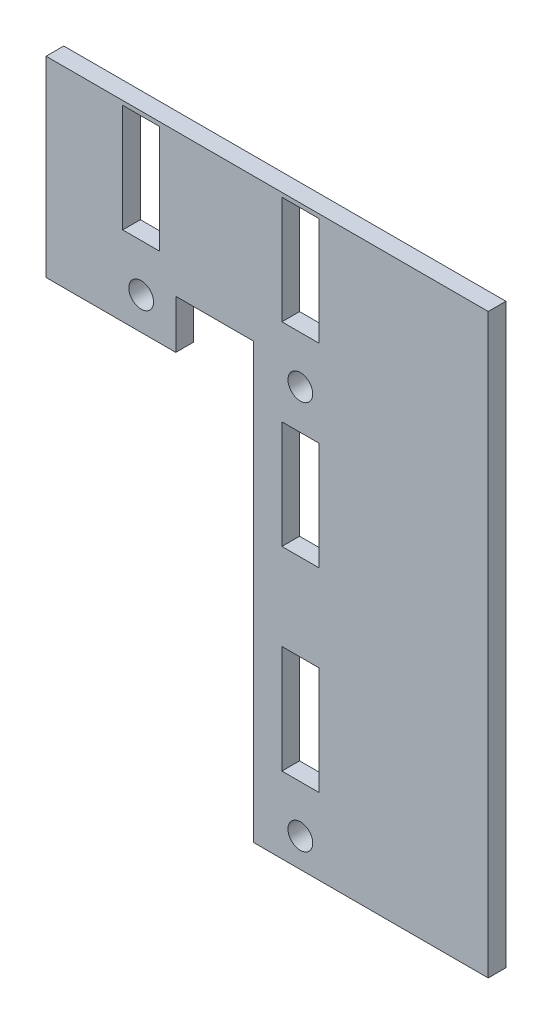
SolidWorks part; units mm, degrees
ref_plane "Front Plane" through (0, 0, 0) normal (1, 0, 0) x (0, 1, 0)
ref_plane "Top Plane" through (0, 0, 0) normal (0, 0, 1) x (0, 1, 0)
ref_plane "Right Plane" through (0, 0, 0) normal (0, 1, 0) x (-1, 0, 0)
sketch "Sketch1" plane through (0, 0, 0) normal (0, 0, 1) x (0, 1, 0)
  line L1 (-50.8, 25.4) -> (50.8, 25.4)
  line L2 (-50.8, 25.4) -> (-50.8, -25.4)
  line L3 (-50.8, -25.4) -> (50.8, -25.4)
  line L4 (50.8, 25.4) -> (50.8, -25.4)
  line L5 (-50.8, 25.4) -> (50.8, -25.4) construction
  line L6 (-50.8, -25.4) -> (50.8, 25.4) construction
  point P0 (0, 0)
  dimension "D1" = 101.6
  dimension "D2" = 50.8
extrude "Boss-Extrude1" add sketch "Sketch1" along normal blind 2.54
sketch "Sketch2" plane through (0, 0, 2.54) normal (0, 0, 1) x (1, 0, 0)
  line L0 (11.1159, -27.94) -> (11.1159, 27.94) construction
  line L1 (11.1159, 27.94) -> (-11.7441, 27.94) construction
  line L2 (-11.7441, 27.94) -> (-11.7441, -27.94) construction
  line L3 (-11.7441, -27.94) -> (11.1159, -27.94) construction
  line L4 (25.4, 50.8) -> (-25.4, 50.8) construction
  circle A0 centre (11.1159, 27.94) radius 1.778
  circle A1 centre (11.1159, -27.94) radius 1.778
  circle A2 centre (-11.7441, 27.94) radius 1.778
  dimension "D3" = 3.556
  dimension "D1" = 55.88
  dimension "D2" = 22.86
  dimension "D4" = 22.86
extrude "Cut-Extrude1" cut sketch "Sketch2" against normal through all
sketch "Sketch3" plane through (0, 0, 2.54) normal (0, 0, 1) x (1, 0, 0)
  line L0 (11.1159, -27.94) -> (11.1159, 27.94) construction
  line L1 (13.7659, -5.68) -> (8.4659, -5.68)
  line L2 (13.7659, -5.68) -> (13.7659, -21.18)
  line L3 (13.7659, -21.18) -> (8.4659, -21.18)
  line L4 (8.4659, -5.68) -> (8.4659, -21.18)
  line L5 (13.7659, -5.68) -> (8.4659, -21.18) construction
  line L6 (13.7659, -21.18) -> (8.4659, -5.68) construction
  line L7 (13.7659, 6.76) -> (8.4659, 6.76)
  line L8 (13.7659, 6.76) -> (13.7659, 22.26)
  line L9 (13.7659, 22.26) -> (8.4659, 22.26)
  line L10 (8.4659, 6.76) -> (8.4659, 22.26)
  line L11 (13.7659, 6.76) -> (8.4659, 22.26) construction
  line L12 (13.7659, 22.26) -> (8.4659, 6.76) construction
  line L13 (13.7659, 34.7) -> (8.4659, 34.7)
  line L14 (13.7659, 34.7) -> (13.7659, 50.2)
  line L15 (13.7659, 50.2) -> (8.4659, 50.2)
  line L16 (8.4659, 34.7) -> (8.4659, 50.2)
  line L17 (13.7659, 34.7) -> (8.4659, 50.2) construction
  line L18 (13.7659, 50.2) -> (8.4659, 34.7) construction
  line L19 (-9.0941, 34.7) -> (-14.3941, 34.7)
  line L20 (-9.0941, 34.7) -> (-9.0941, 50.2)
  line L21 (-9.0941, 50.2) -> (-14.3941, 50.2)
  line L22 (-14.3941, 34.7) -> (-14.3941, 50.2)
  line L23 (-9.0941, 34.7) -> (-14.3941, 50.2) construction
  line L24 (-9.0941, 50.2) -> (-14.3941, 34.7) construction
  circle A0 centre (11.1159, -27.94) radius 1.778 construction
  point P0 (11.1159, -13.43)
  point P10 (11.1159, 14.51)
  point P14 (11.1159, 42.45)
  point P19 (-11.7441, 42.45)
  dimension "D1" = 6.76
  dimension "D3" = 15.5
  dimension "D4" = 27.94
  dimension "D5" = 27.94
  dimension "D6" = 22.86
  dimension "D7" = 5.3
extrude "Cut-Extrude4" cut sketch "Sketch3" against normal through all
sketch "Sketch5" plane through (0, 0, 2.54) normal (0, 0, 1) x (1, 0, 0)
  line L0 (4.4019, -32.102) -> (4.4019, 30.255)
  line L1 (-25.4, -50.8) -> (25.4, -50.8) construction
  line L2 (4.4019, 30.255) -> (-6.7741, 30.255)
  line L3 (-6.7741, 30.255) -> (-6.7741, 23.27)
  line L4 (-6.7741, 23.27) -> (-25.4, 23.27)
  line L5 (-25.4, 50.8) -> (-25.4, -50.8) construction
  line L6 (-25.4, 23.27) -> (-25.4, -50.8)
  line L7 (-25.4, -50.8) -> (25.4, -50.8)
  line L8 (4.4019, -32.102) -> (25.4, -32.102)
  line L9 (25.4, -50.8) -> (25.4, 50.8) construction
  line L10 (25.4, -32.102) -> (25.4, -50.8)
  line L11 (8.4659, -21.18) -> (13.7659, -21.18) construction
  dimension "D1" = 4.064
  dimension "D2" = 4.445
  dimension "D3" = 11.43
  dimension "D4" = 15.24
  dimension "D5" = 10.922
extrude "Cut-Extrude5" cut sketch "Sketch5" against normal through all
sketch "Sketch6" plane through (0, 0, 2.54) normal (0, 0, 1) x (1, 0, 0)
  line L7 (25.4, 50.8) -> (38.1, 50.8)
  line L8 (25.4, 50.8) -> (25.4, -32.102)
  line L9 (25.4, -32.102) -> (38.1, -32.102)
  line L10 (38.1, 50.8) -> (38.1, -32.102)
  line L11 (25.4, 50.8) -> (38.1, -32.102) construction
  line L12 (25.4, -32.102) -> (38.1, 50.8) construction
  line L13 (25.4, -32.102) -> (4.4019, -32.102) construction
  point P10 (31.75, 9.349)
  dimension "D2" = 12.7
extrude "Boss-Extrude5" add sketch "Sketch6" along direction (0, 0, 1) on the side against the normal blind 2.54
